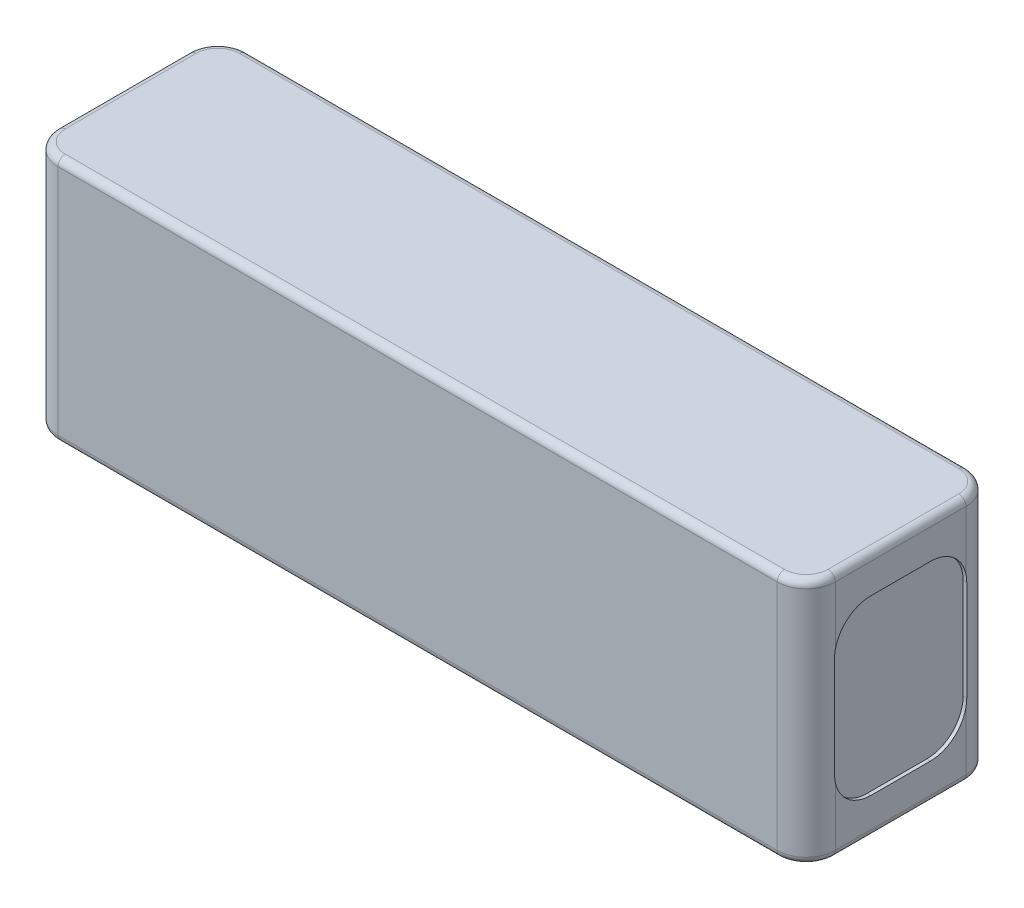
SolidWorks part; units mm, degrees
ref_plane "Front Plane" through (0, 0, 0) normal (0, 0, 1) x (1, 0, 0)
ref_plane "Top Plane" through (0, 0, 0) normal (0, 1, 0) x (1, 0, 0)
ref_plane "Right Plane" through (0, 0, 0) normal (1, 0, 0) x (0, 0, -1)
ref_plane "Plane1" through (0, 0, -15) normal (0, 0, -1) x (-1, 0, 0)
sketch "Sketch1" plane through (0, 0, -15) normal (0, 0, -1) x (-1, 0, 0)
  line L0 (-69, -22) -> (38, -22)
  line L1 (38, -22) -> (38, 12)
  line L2 (38, 12) -> (-69, 12)
  line L3 (-69, 12) -> (-69, -22)
  line L4 (-69, -5) -> (38, -5) construction
  line L5 (-15.5, 12) -> (-15.5, -22) construction
  dimension "D1" = 34
  dimension "D2" = 107
extrude "Boss-Extrude1" add sketch "Sketch1" against normal blind 26
sketch "Sketch2" plane through (69, 0, 0) normal (1, 0, 0) x (0, 0, -1)
  line L0 (-7.1, 1.9) -> (-7.1, -11.9)
  line L1 (-2.1, -16.9) -> (6.1, -16.9)
  line L2 (11.1, -11.9) -> (11.1, 1.9)
  line L3 (6.1, 6.9) -> (-2.1, 6.9)
  line L4 (-11, 12) -> (15, -22) construction
  line L5 (15, 12) -> (-11, -22) construction
  line L6 (-7.1, 6.9) -> (11.1, -16.9) construction
  line L7 (11.1, 6.9) -> (-7.1, -16.9) construction
  line L12 (-11, 12) -> (15, 12) construction
  line L13 (-11, 12) -> (-11, -22) construction
  line L14 (-11, -22) -> (15, -22) construction
  line L15 (15, 12) -> (15, -22) construction
  line L16 (-11, 12) -> (15, -22) construction
  line L17 (-11, -22) -> (15, 12) construction
  arc A0 (-7.1, -11.9) -> (-2.1, -16.9) centre (-2.1, -11.9) ccw
  arc A1 (6.1, -16.9) -> (11.1, -11.9) centre (6.1, -11.9) ccw
  arc A2 (11.1, 1.9) -> (6.1, 6.9) centre (6.1, 1.9) ccw
  arc A3 (-7.1, 1.9) -> (-2.1, 6.9) centre (-2.1, 1.9) cw
  point P16 (2, -5)
  dimension "D2" = 26
  dimension "D3" = 5
  dimension "D1" = 18.2
extrude "Cut-Extrude1" cut sketch "Sketch2" against normal blind 0.5
sketch "Sketch3" plane through (-38, 0, 0) normal (-1, 0, 0) x (0, 0, 1)
  line L0 (-0.25, 7.75) -> (-3.75, 7.75)
  line L1 (-11.75, -0.25) -> (-11.75, -9.75)
  line L2 (-3.75, -17.75) -> (-0.25, -17.75)
  line L3 (7.75, -9.75) -> (7.75, -0.25)
  line L4 (-11.75, 7.75) -> (7.75, -17.75) construction
  line L5 (7.75, 7.75) -> (-11.75, -17.75) construction
  line L6 (-15, 12) -> (11, -22) construction
  line L7 (11, -22) -> (-15, -22) construction
  line L8 (-15, -22) -> (11, 12) construction
  arc A0 (-11.75, -9.75) -> (-3.75, -17.75) centre (-3.75, -9.75) ccw
  arc A1 (-0.25, -17.75) -> (7.75, -9.75) centre (-0.25, -9.75) ccw
  arc A2 (-0.25, 7.75) -> (7.75, -0.25) centre (-0.25, -0.25) cw
  arc A3 (-3.75, 7.75) -> (-11.75, -0.25) centre (-3.75, -0.25) ccw
  dimension "D3" = 8
  dimension "D1" = 19.5
  dimension "D2" = 26
extrude "Cut-Extrude2" cut sketch "Sketch3" against normal blind 0.5
fillet "Fillet1" radius 4 4 edges at (-38, -5, -15) (-38, -5, 11) (69, -5, -15) (69, -5, 11) tangent propagation no
fillet "Fillet2" radius 1 16 edges at (67.8284, 12, -13.8284) (69, 12, -2) (15.5, 12, -15) (67.8284, 12, 9.8284) (-36.8284, 12, -13.8284) (15.5, 12, 11) (-38, 12, -2) (-36.8284, 12, 9.8284) (-38, -22, -2) (-36.8284, -22, -13.8284) (-36.8284, -22, 9.8284) (15.5, -22, -15) (15.5, -22, 11) (67.8284, -22, -13.8284) (67.8284, -22, 9.8284) (69, -22, -2) tangent propagation no
sketch "Sketch4" [suppressed] plane through (0, 0, 10) normal (0, 0, 1) x (1, 0, 0)
  line L0 (-75, 4) -> (65, 4) construction
  line L1 (-75, 29) -> (-75, -21) construction
  line L2 (65, -21) -> (65, 29) construction
  line L3 (-5, 25.9735) -> (-5, -21) construction
  line L4 (-75, -21) -> (65, -21) construction
  circle A0 centre (-5, 4) radius 0.5026
sketch "Sketch5" plane through (68.5, 0, 0) normal (1, 0, 0) x (0, 0, -1)
  line L0 (7, 8) -> (-3, 8) construction
  line L1 (2, 12) -> (2, 8) construction
  line L2 (-7, 12) -> (11, 12) construction
  circle A0 centre (-3, 8) radius 2
  circle A1 centre (7, 8) radius 2
  dimension "D1" = 4
  dimension "D2" = 10
  dimension "D3" = 4
equation "\"D1@Sketch3\"=\"D2@Sketch3\" * .75"
equation "\"D1@Sketch2\"=\"D2@Sketch2\"* .7"
